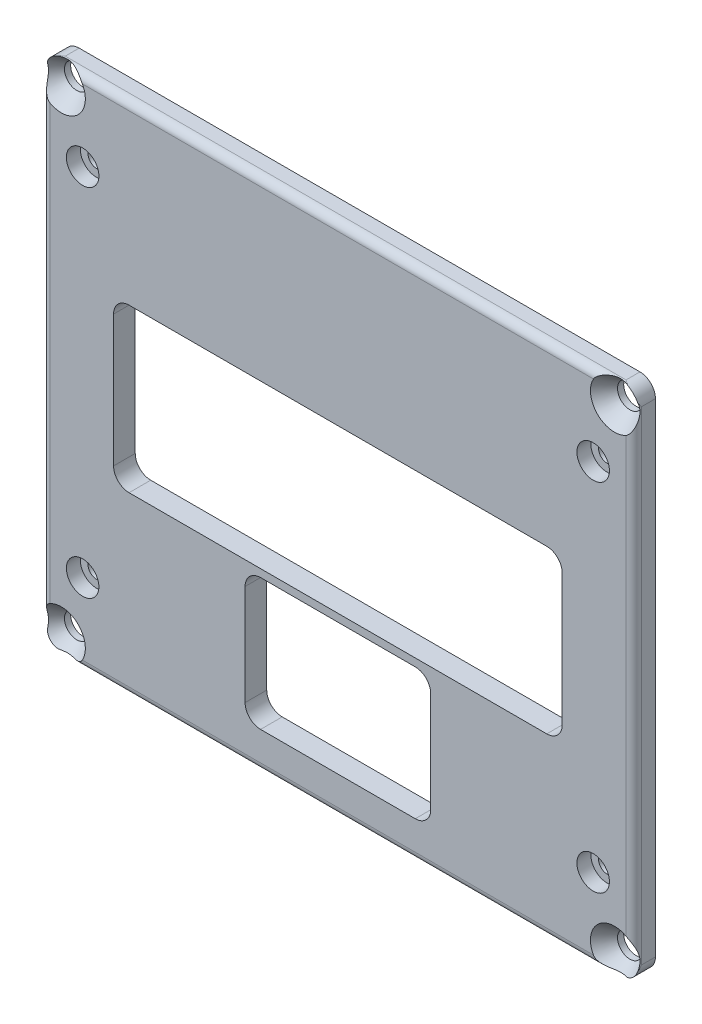
SolidWorks part; units mm, degrees
ref_plane "Front Plane" through (0, 0, 0) normal (1, 0, 0) x (0, 1, 0)
ref_plane "Top Plane" through (0, 0, 0) normal (0, 0, 1) x (0, 1, 0)
ref_plane "Right Plane" through (0, 0, 0) normal (0, 1, 0) x (-1, 0, 0)
sketch "Sketch1" plane through (0, 0, 0) normal (0, 0, 1) x (0, 1, 0)
  line L0 (-23, 0) -> (23, 0) construction
  line L1 (-23, 33) -> (23, 33) construction
  line L2 (-23, 33) -> (-23, -33) construction
  line L3 (-23, -33) -> (23, -33) construction
  line L4 (23, 33) -> (23, -33) construction
  line L5 (0, 33) -> (0, -33) construction
  line L6 (-10.5, 0) -> (-10.5, -27)
  line L7 (-30.75, 35.75) -> (30.75, 35.75) construction
  line L8 (-30.75, 35.75) -> (-30.75, -35.75) construction
  line L9 (-30.75, -35.75) -> (30.75, -35.75) construction
  line L10 (30.75, 35.75) -> (30.75, -35.75) construction
  line L11 (-31.25, 38.25) -> (31.25, 38.25)
  line L12 (-33.25, 36.25) -> (-33.25, -36.25)
  line L13 (-31.25, -38.25) -> (31.25, -38.25)
  line L14 (33.25, 36.25) -> (33.25, -36.25)
  line L15 (-8.5, 29) -> (8.5, 29)
  line L16 (-10.5, 27) -> (-10.5, 0)
  line L17 (-8.5, -29) -> (8.5, -29)
  line L18 (10.5, 27) -> (10.5, -27)
  line L19 (-26.5, 12) -> (-13.5, 12)
  line L20 (-28.5, 10) -> (-28.5, -10)
  line L21 (-26.5, -12) -> (-13.5, -12)
  line L23 (-11.5, 10) -> (-11.5, -10)
  circle A0 centre (-23, 33) radius 1.1
  circle A1 centre (23, 33) radius 1.1
  circle A2 centre (23, -33) radius 1.1
  circle A3 centre (-23, -33) radius 1.1
  circle A4 centre (-30.75, 35.75) radius 1.6
  circle A5 centre (30.75, 35.75) radius 1.6
  circle A6 centre (30.75, -35.75) radius 1.6
  circle A7 centre (-30.75, -35.75) radius 1.6
  arc A8 (31.25, -38.25) -> (33.25, -36.25) centre (31.25, -36.25) ccw
  arc A9 (-33.25, -36.25) -> (-31.25, -38.25) centre (-31.25, -36.25) ccw
  arc A10 (31.25, 38.25) -> (33.25, 36.25) centre (31.25, 36.25) cw
  arc A11 (-31.25, 38.25) -> (-33.25, 36.25) centre (-31.25, 36.25) ccw
  arc A12 (-10.5, -27) -> (-8.5, -29) centre (-8.5, -27) ccw
  arc A13 (8.5, -29) -> (10.5, -27) centre (8.5, -27) ccw
  arc A14 (8.5, 29) -> (10.5, 27) centre (8.5, 27) cw
  arc A15 (-8.5, 29) -> (-10.5, 27) centre (-8.5, 27) ccw
  arc A18 (-28.5, -10) -> (-26.5, -12) centre (-26.5, -10) ccw
  arc A19 (-26.5, 12) -> (-28.5, 10) centre (-26.5, 10) ccw
  arc A20 (-13.5, -12) -> (-11.5, -10) centre (-13.5, -10) ccw
  arc A21 (-13.5, 12) -> (-11.5, 10) centre (-13.5, 10) cw
  circle A22 centre (-23, 33) radius 2.1
  circle A23 centre (23, 33) radius 2.1
  circle A24 centre (23, -33) radius 2.1
  circle A25 centre (-23, -33) radius 2.1
  point P40 (-10.5, -29)
  point P45 (10.5, 29)
  point P48 (-10.5, 29)
  point P55 (-10.5, 12)
  point P57 (-12, 0)
  point P58 (-10.5, -12)
  point P61 (-28.5, -12)
  point P64 (-28.5, 12)
  point P66 (0, 0)
  point P67 (-12, -3.4322)
  point P68 (0, 0)
  dimension "D1" = 2.2
  dimension "D6" = 3.2
  dimension "D7" = 2.5
  dimension "D8" = 2.5
  dimension "D9" = 2
  dimension "D12" = 2
  dimension "D15" = 2
  dimension "D2" = 46
  dimension "D3" = 66
  dimension "D4" = 71.5
  dimension "D5" = 61.5
  dimension "D10" = 58
  dimension "D11" = 21
  dimension "D13" = 18
  dimension "D14" = 24
  dimension "D16" = 1
  dimension "D17" = 1
extrude "Boss-Extrude1" add sketch "Sketch1" along normal blind 2.8 contours L11 A11 L12 A9 L13 A8 L14 A10 A19 L19 L16 A15 L15 A14 L18 A13 L17 A12 L6 L21 A18 L20 A0 A1 A2 A3 A4 A5 A6 A7 | A22 | A23 | A25 | A24 region at (-37.2364, 0, 0)
extrude "Cut-Extrude2" cut sketch "Sketch1<6>" against normal blind 1.8 from surface contours A22 | A23 | A24 | A25 starting at face at (0, 0, 2.8)
sketch "Sketch1<6>" plane through (0, 0, 0) normal (0, 0, 1) x (0, 1, 0) same geometry as "Sketch1"
extrude "Cut-Extrude1" cut sketch "Sketch1<3>" against normal through all draft 5 from surface contours A3 | A0 | A1 | A2 region at (-33, -23, 0) region at (33, -23, 0) starting at face at (35.1, 23, 1)
sketch "Sketch1<3>" plane through (0, 0, 0) normal (0, 0, 1) x (0, 1, 0) same geometry as "Sketch1"
chamfer "Chamfer1" distance 1.5 distance2 2 4 edges at (-34.15, -30.75, 2.8) (37.35, -30.75, 2.8) (37.35, 30.75, 2.8) (-34.15, 30.75, 2.8) first distance on face at (35.1, -23, 2.8)
fillet "Fillet1" radius 1 4 edges at (-38.25, 0, 2.8) (0, -33.25, 2.8) (38.25, 0, 2.8) (0, 33.25, 2.8)
